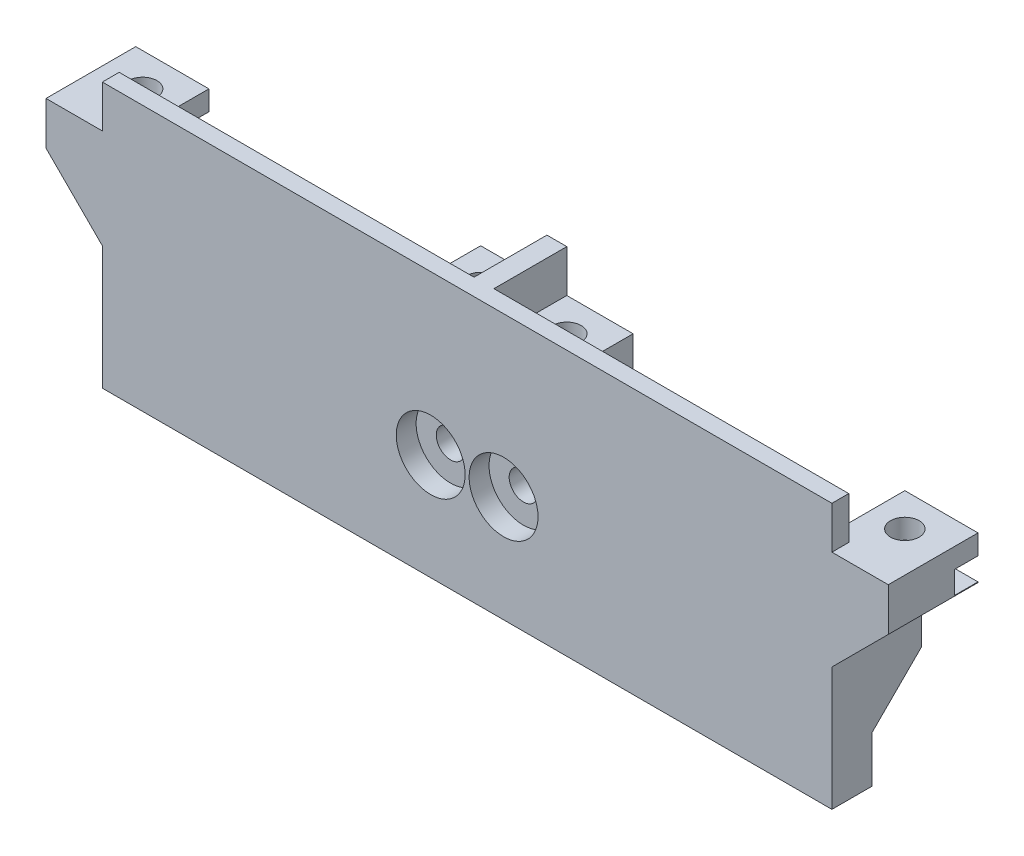
SolidWorks part; units mm, degrees
note: The reader was unsure of these and kept them because the rebuilt part matched: shared geometry of "Sketch8<2>", "Sketch10<3>", "Sketch11<3>".
ref_plane "Front Plane" through (0, 0, 0) normal (0, 0, 1) x (1, 0, 0)
ref_plane "Top Plane" through (0, 0, 0) normal (0, 1, 0) x (1, 0, 0)
ref_plane "Right Plane" through (0, 0, 0) normal (1, 0, 0) x (0, 0, -1)
sketch "Sketch1" plane through (0, 0, 0) normal (0, 1, 0) x (1, 0, 0)
  line L0 (-23.04, -8.04) -> (-23.04, 5.5)
  line L1 (-20.5, -5.5) -> (20.5, -5.5)
  line L2 (-20.5, -5.5) -> (-20.5, 5.5)
  line L3 (-20.5, 5.5) -> (20.5, 5.5) construction
  line L4 (20.5, -5.5) -> (20.5, 5.5)
  line L5 (-20.5, -5.5) -> (20.5, 5.5) construction
  line L6 (-20.5, 5.5) -> (20.5, -5.5) construction
  line L7 (-23.04, -8.04) -> (23.04, -8.04)
  line L8 (23.04, -8.04) -> (23.04, 5.5) construction
  line L9 (-20.5, 5.5) -> (-23.04, 5.5)
  line L10 (20.5, 5.5) -> (23.04, 5.5)
  line L11 (40.96, -8.04) -> (40.96, 5.5) construction
  line L12 (43.5, -5.5) -> (84.5, -5.5)
  line L13 (43.5, -5.5) -> (43.5, 5.5)
  line L14 (84.5, -5.5) -> (84.5, 5.5)
  line L15 (40.96, -8.04) -> (87.04, -8.04)
  line L16 (87.04, -8.04) -> (87.04, 5.5)
  line L17 (43.5, 5.5) -> (40.96, 5.5)
  line L18 (84.5, 5.5) -> (87.04, 5.5)
  line L19 (0, 0) -> (64, 0) construction
  line L20 (23.04, -8.04) -> (40.96, -8.04)
  line L21 (23.04, 5.5) -> (40.96, 5.5)
  line L22 (32, 5.5) -> (32, -8.04) construction
  line L23 (28.0981, -4) -> (30.6962, 0.5) construction
  line L24 (30.6962, 0.5) -> (28.0981, 5) construction
  line L25 (28.0981, 5) -> (22.9019, 5) construction
  line L26 (22.9019, 5) -> (20.3038, 0.5) construction
  line L27 (20.3038, 0.5) -> (22.9019, -4) construction
  line L28 (22.9019, -4) -> (28.0981, -4) construction
  line L29 (35.9019, -4) -> (33.3038, 0.5) construction
  line L30 (41.0981, -4) -> (35.9019, -4) construction
  line L31 (43.6962, 0.5) -> (41.0981, -4) construction
  line L32 (41.0981, 5) -> (43.6962, 0.5) construction
  line L33 (35.9019, 5) -> (41.0981, 5) construction
  line L34 (33.3038, 0.5) -> (35.9019, 5) construction
  circle A1 centre (25.5, 0.5) radius 4.5 construction
  circle A2 centre (25.5, 0.5) radius 2.16
  circle A3 centre (38.5, 0.5) radius 2.16
  point P0 (0, 0)
  point P11 (64, 0)
  dimension "D9" = 4.32
  dimension "D2" = 41
  dimension "D3" = 11
  dimension "D5" = 64
  dimension "D6" = 5
  dimension "D7" = 5
  dimension "D8" = 9
  dimension "D1" = 2.54
  dimension "D4" = 2
extrude "Boss-Extrude1" add sketch "Sketch1" along normal blind 26.61
ref_plane "Plane1" through (0, 21.61, 0) normal (0, 1, 0) x (1, 0, 0)
sketch "Sketch3" plane through (0, 21.61, 0) normal (0, 1, 0) x (1, 0, 0)
  line L0 (20.5, 5.5) -> (20.5, -5.5) construction
  line L1 (28.0981, -4) -> (30.6962, 0.5)
  line L2 (30.6962, 0.5) -> (28.0981, 5)
  line L3 (28.0981, 5) -> (22.9019, 5) construction
  line L4 (22.9019, 5) -> (20.3038, 0.5) construction
  line L5 (20.3038, 0.5) -> (22.9019, -4) construction
  line L6 (22.9019, -4) -> (28.0981, -4)
  line L7 (41.0981, -4) -> (43.6962, 0.5) construction
  line L8 (43.6962, 0.5) -> (41.0981, 5) construction
  line L9 (41.0981, 5) -> (35.9019, 5) construction
  line L10 (35.9019, 5) -> (33.3038, 0.5)
  line L11 (33.3038, 0.5) -> (35.9019, -4)
  line L12 (35.9019, -4) -> (41.0981, -4)
  line L13 (43.5, -5.5) -> (43.5, 5.5) construction
  line L14 (43.5, 5.5) -> (20.5, 5.5) construction
  line L15 (43.5, -4) -> (43.5, 5.5)
  line L16 (20.5, 5.5) -> (20.5, -4)
  line L17 (43.5, 5.5) -> (36.1906, 5.5)
  line L18 (22.9019, -4) -> (20.5, -4)
  line L19 (28.0981, 5) -> (27.8094, 5.5)
  line L20 (41.0981, -4) -> (43.5, -4)
  line L21 (35.9019, 5) -> (36.1906, 5.5)
  line L22 (27.8094, 5.5) -> (20.5, 5.5)
  circle A0 centre (38.5, 0.5) radius 2.16 construction
  circle A1 centre (25.5, 0.5) radius 2.16 construction
  circle A2 centre (38.5, 0.5) radius 2.16 construction
  circle A3 centre (25.5, 0.5) radius 2.16 construction
  circle A4 centre (25.5, 0.5) radius 4.5 construction
  circle A5 centre (38.5, 0.5) radius 4.5 construction
  dimension "D1" = 9
extrude "Cut-Extrude1" cut sketch "Sketch3" against normal blind 3.5
sketch "Sketch4" plane through (-23.04, 0, 0) normal (-1, 0, 0) x (0, 0, 1)
  line L0 (-5.5, 7.5) -> (2, 0)
  line L1 (-5.5, 26.61) -> (-5.5, 0) construction
  line L2 (-5.5, 0) -> (8.04, 0) construction
  line L3 (2, 0) -> (-5.5, 0)
  line L4 (-5.5, 0) -> (-5.5, 7.5)
  dimension "D1" = 7.5
extrude "Cut-Extrude2" cut sketch "Sketch4" against normal blind 4
ref_plane "Plane2" through (32, 0, 0) normal (1, 0, 0) x (0, 0, -1)
mirror "Mirror1" about plane through (32, 0, 0) normal (1, 0, 0) of "Cut-Extrude2"
sketch "Sketch5" plane through (0, 0, 0) normal (0, -1, 0) x (1, 0, 0)
  line L1 (-23.04, 8.04) -> (87.04, 8.04)
  line L2 (-23.04, 8.04) -> (-23.04, -5.5)
  line L3 (-23.04, -5.5) -> (87.04, -5.5)
  line L4 (87.04, 8.04) -> (87.04, -5.5)
  circle A0 centre (38.5, -0.5) radius 2.16 construction
  circle A1 centre (25.5, -0.5) radius 2.16 construction
  circle A2 centre (38.5, -0.5) radius 2.16
  circle A3 centre (25.5, -0.5) radius 2.16
extrude "Boss-Extrude2" add sketch "Sketch5" along normal blind 7
sketch "Sketch6" plane through (0, 26.61, 0) normal (0, 1, 0) x (1, 0, 0)
  line L0 (-23.04, -5.5) -> (30.5, -5.5)
  line L1 (-23.04, 5.5) -> (-23.04, -8.04) construction
  line L2 (30.5, -5.5) -> (30.5, 5.5)
  line L3 (43.5, 5.5) -> (20.5, 5.5) construction
  line L4 (30.5, 5.5) -> (33.5, 5.5)
  line L5 (-23.04, -5.5) -> (-23.04, -8.04)
  line L6 (-23.04, -8.04) -> (87.04, -8.04)
  line L7 (-23.04, -8.04) -> (87.04, -8.04) construction
  line L8 (20.5, -5.5) -> (-20.5, -5.5) construction
  line L9 (32, -6.05) -> (32, 6.05) construction
  line L10 (87.04, -5.5) -> (87.04, -8.04)
  line L11 (33.5, -5.5) -> (33.5, 5.5)
  line L12 (87.04, -5.5) -> (33.5, -5.5)
  point P19 (32, -8.04)
  point P21 (32, 5.5)
  dimension "D1" = 1.5
extrude "Boss-Extrude3" add sketch "Sketch6" along normal offset from surface (6.39 mm away) 40 up to face at (38.5, -7, -2.66)
sketch "Sketch7" plane through (0, 0, 8.04) normal (0, 0, 1) x (1, 0, 0)
  line L1 (-23.04, 26.61) -> (-31.54, 26.61)
  line L2 (-23.04, 33) -> (-23.04, 26.61) construction
  line L3 (-23.04, 33) -> (-23.04, 26.61) construction
  line L4 (-31.54, 26.61) -> (-31.54, 20.11)
  line L5 (-31.54, 20.11) -> (-23.04, 11.61)
  line L6 (-23.04, 33) -> (-23.04, -7) construction
  line L7 (-23.04, 11.61) -> (-23.04, 26.61)
  dimension "D1" = 45
  dimension "D2" = 8.5
  dimension "D3" = 6.5
extrude "Boss-Extrude4" add sketch "Sketch7" against normal up to surface (13.54 mm away) up to face at (-21.77, 17.055, -5.5)
sketch "Sketch8" plane through (0, 21.61, 0) normal (0, 1, 0) x (1, 0, 0)
  line L0 (-20.5, -5.5) -> (-20.5, 5.5) construction
  line L1 (-30.6962, 0.5) -> (-31.54, 1.9616)
  line L2 (-22.9019, -4) -> (-20.3038, 0.5) construction
  line L3 (-20.3038, 0.5) -> (-22.9019, 5) construction
  line L4 (-22.9019, 5) -> (-28.0981, 5) construction
  line L5 (-28.0981, 5) -> (-30.6962, 0.5) construction
  line L6 (-30.6962, 0.5) -> (-28.0981, -4)
  line L7 (-28.0981, -4) -> (-22.9019, -4)
  line L8 (-31.54, 5.5) -> (-31.54, -8.04) construction
  line L9 (-31.54, 1.9616) -> (-31.54, 5.5)
  line L10 (-31.54, 5.5) -> (-20.5, 5.5)
  line L11 (-20.5, 5.5) -> (-20.5, 0.1603)
  line L12 (-20.5, 0.1603) -> (-22.9019, -4)
  circle A0 centre (-25.5, 0.5) radius 2.16
  circle A1 centre (25.5, 0.5) radius 2.16 construction
  circle A2 centre (25.5, 0.5) radius 2.16 construction
  circle A3 centre (-25.5, 0.5) radius 4.5 construction
  dimension "D1" = 5
  dimension "D2" = 9
extrude "Cut-Extrude3" cut sketch "Sketch8" along normal blind 2 and the other way blind 1.4
extrude "Cut-Extrude4" cut sketch "Sketch8<2>" against normal through all both and the other way through all contours A0
sketch "Sketch8<2>" plane through (0, 21.61, 0) normal (0, 1, 0) x (1, 0, 0) same geometry as "Sketch8"
mirror "Mirror2" about plane through (32, 0, 0) normal (1, 0, 0) of "Cut-Extrude4", "Cut-Extrude3", "Boss-Extrude4"
chamfer "Chamfer2" distance 2 angle 45 2 edges at (-20.5, 3.75, -1.75) (84.5, 3.75, -1.75)
sketch "Sketch10" plane through (0, 0, 8.04) normal (0, 0, 1) x (1, 0, 0)
  line L0 (32, -6.05) -> (32, 6.05) construction
  line L1 (20.5, 9.055) -> (26.5, 9.055) construction
  line L3 (31.6962, 9.055) -> (29.0981, 13.555) construction
  line L4 (29.0981, 13.555) -> (23.9019, 13.555) construction
  line L5 (23.9019, 13.555) -> (21.3038, 9.055) construction
  line L6 (21.3038, 9.055) -> (23.9019, 4.555) construction
  line L7 (23.9019, 4.555) -> (29.0981, 4.555) construction
  line L8 (29.0981, 4.555) -> (31.6962, 9.055) construction
  line L9 (32.3038, 9.055) -> (34.9019, 4.555) construction
  line L10 (34.9019, 4.555) -> (40.0981, 4.555) construction
  line L11 (40.0981, 4.555) -> (42.6962, 9.055) construction
  line L12 (42.6962, 9.055) -> (40.0981, 13.555) construction
  line L13 (40.0981, 13.555) -> (34.9019, 13.555) construction
  line L14 (34.9019, 13.555) -> (32.3038, 9.055) construction
  line L20 (27.8094, 18.11) -> (20.5, 18.11)
  line L21 (27.8094, 21.61) -> (27.8094, 18.11)
  line L22 (20.5, 21.61) -> (27.8094, 21.61)
  line L23 (20.5, 26.61) -> (20.5, 21.61)
  line L24 (30.5, 26.61) -> (20.5, 26.61)
  line L25 (30.5, 33) -> (30.5, 26.61)
  line L26 (33.5, 33) -> (30.5, 33)
  line L27 (33.5, 26.61) -> (33.5, 33)
  line L28 (43.5, 26.61) -> (33.5, 26.61)
  line L29 (43.5, 21.61) -> (43.5, 26.61)
  line L30 (36.1906, 21.61) -> (43.5, 21.61)
  line L31 (36.1906, 18.11) -> (36.1906, 21.61)
  line L32 (43.5, 18.11) -> (36.1906, 18.11)
  line L33 (43.5, 0) -> (43.5, 18.11)
  line L34 (87.04, 0) -> (43.5, 0)
  line L35 (87.04, -7) -> (87.04, 0)
  line L36 (-23.04, -7) -> (87.04, -7)
  line L37 (-23.04, 0) -> (-23.04, -7)
  line L38 (20.5, 0) -> (-23.04, 0)
  line L39 (20.5, 18.11) -> (20.5, 0)
  line L40 (27.8094, 18.11) -> (20.5, 18.11) construction
  line L41 (27.8094, 21.61) -> (27.8094, 18.11) construction
  line L42 (20.5, 21.61) -> (27.8094, 21.61) construction
  line L43 (20.5, 26.61) -> (20.5, 21.61) construction
  line L44 (30.5, 26.61) -> (20.5, 26.61) construction
  line L45 (30.5, 33) -> (30.5, 26.61) construction
  line L46 (33.5, 33) -> (30.5, 33) construction
  line L47 (33.5, 26.61) -> (33.5, 33) construction
  line L48 (43.5, 26.61) -> (33.5, 26.61) construction
  line L49 (43.5, 21.61) -> (43.5, 26.61) construction
  line L50 (36.1906, 21.61) -> (43.5, 21.61) construction
  line L51 (36.1906, 18.11) -> (36.1906, 21.61) construction
  line L52 (43.5, 18.11) -> (36.1906, 18.11) construction
  line L53 (43.5, 0) -> (43.5, 18.11) construction
  line L54 (87.04, 0) -> (43.5, 0) construction
  line L55 (87.04, -7) -> (87.04, 0) construction
  line L56 (-23.04, -7) -> (87.04, -7) construction
  line L57 (-23.04, 0) -> (-23.04, -7) construction
  line L58 (20.5, 0) -> (-23.04, 0) construction
  line L59 (20.5, 18.11) -> (20.5, 0) construction
  circle A0 centre (26.5, 9.055) radius 2.16
  circle A1 centre (37.5, 9.055) radius 2.16
  circle A2 centre (26.5, 9.055) radius 4.5 construction
  circle A3 centre (37.5, 9.055) radius 4.5 construction
  circle A4 centre (26.5, 9.055) radius 5.1962
  circle A5 centre (37.5, 9.055) radius 5.1962
  dimension "D2" = 4.32
  dimension "D3" = 6
  dimension "D4" = 9
  dimension "D1" = 0
extrude "Cut-Extrude5" cut sketch "Sketch10" against normal through all both and the other way through all contours A0 | A1
extrude "Cut-Extrude6" cut sketch "Sketch10<3>" against normal blind 3
sketch "Sketch10<3>" plane through (0, 0, 8.04) normal (0, 0, 1) x (1, 0, 0) same geometry as "Sketch10"
sketch "Sketch11" plane through (0, 0, -5.5) normal (0, 0, -1) x (-1, 0, 0)
  line L0 (23.04, -7) -> (-87.04, -7) construction
  line L1 (-87.04, 0) -> (-59.96, 0)
  line L2 (-87.04, 0) -> (-87.04, -7)
  line L3 (-87.04, -7) -> (-59.96, -7)
  line L4 (-59.96, 0) -> (-59.96, -7)
  line L5 (-32, 6.05) -> (-32, -6.05) construction
  line L6 (-4.04, 0) -> (-4.04, -7)
  line L7 (23.04, -7) -> (-4.04, -7)
  line L8 (23.04, 0) -> (23.04, -7)
  line L9 (23.04, 0) -> (-4.04, 0)
  line M19 (-43.5, 0) -> (-87.04, 0)
  line M20 (-87.04, 0) -> (-87.04, -7)
  line M21 (-87.04, -7) -> (23.04, -7)
  line M22 (23.04, -7) -> (23.04, 0)
  line M23 (23.04, 0) -> (-20.5, 0)
  dimension "D1" = 27.08
extrude "Cut-Extrude7" cut sketch "Sketch11" against normal blind 7.5 contours L4 M19 M20 M21
extrude "Boss-Extrude5" add sketch "Sketch11<3>" along normal blind 7.5 contours L6 M23 M21 M22
sketch "Sketch11<3>" plane through (0, 0, -5.5) normal (0, 0, -1) x (-1, 0, 0) same geometry as "Sketch11"
sketch "Sketch12" plane through (0, -7, 0) normal (0, -1, 0) x (1, 0, 0)
  line L0 (87.04, 8.04) -> (-23.04, 8.04) construction
  line L1 (-23.04, 8.04) -> (-23.04, -13) construction
  circle A0 centre (-9.5, -5.5) radius 3.55
  dimension "D3" = 7.1
  dimension "D1" = 13.54
  dimension "D2" = 13.54
extrude "Cut-Extrude8" cut sketch "Sketch12" against normal blind 7.5
